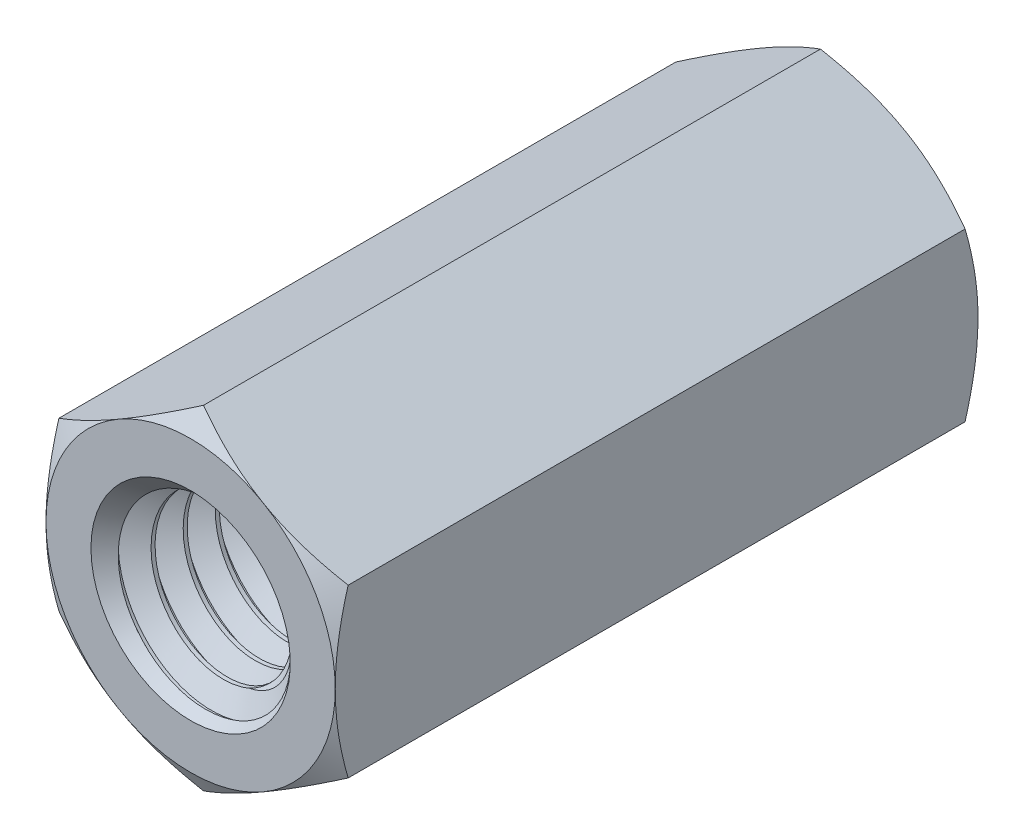
SolidWorks part; units mm, degrees
material "Brass"
ref_plane "Front Plane" through (0, 0, 0) normal (0, 0, 1) x (1, 0, 0)
ref_plane "Top Plane" through (0, 0, 0) normal (0, 1, 0) x (1, 0, 0)
ref_plane "Right Plane" through (0, 0, 0) normal (1, 0, 0) x (0, 0, -1)
sketch "Sketch3" plane through (0, 0, 0) normal (1, 0, 0) x (0, 0, -1)
  line L0 (-5, 0) -> (5, 0) construction
  line L1 (0, 2.25) -> (0, -2.25) construction
  line L2 (-5, 1.5) -> (-5, -1.5) construction
  point P2 (0.2, 0)
  point P3 (-0.2, 0)
  dimension "Length" = 10
  dimension "Min Thread Length" = 4.8
  dimension "D1" = 4.8
  dimension "Thread Dia" = 3
  dimension "Hex" = 4.5
sketch "Sketch1" plane through (0, 0, 0) normal (0, 0, 1) x (1, 0, 0)
  line L1 (0, 2.5981) -> (-2.25, 1.299)
  line L2 (-2.25, 1.299) -> (-2.25, -1.299)
  line L3 (-2.25, -1.299) -> (0, -2.5981)
  line L4 (0, -2.5981) -> (2.25, -1.299)
  line L5 (2.25, -1.299) -> (2.25, 1.299)
  line L6 (2.25, 1.299) -> (0, 2.5981)
  circle A0 centre (0, 0) radius 2.25 construction
  circle A1 centre (0, 0) radius 1.5
extrude "Extrude1" add sketch "Sketch1" along normal up to vertex (5 mm away) and the other way up to vertex (5 mm away) up to point (0, 0, 5) other way up to point (0, 0, -5)
sketch "Sketch11" plane through (0, 0, -5) normal (0, 0, -1) x (-1, 0, 0)
  circle A0 centre (0, 0) radius 1.5 construction
  circle A1 centre (0, 0) radius 1.5
curve "Helix/Spiral1" pitch 0.5 height 10.5 radius 1.5 centre (0, 0, -5) axis (0, 0, 1) start towards (0, 1, 0) parameters "Pitch"=0.5
sketch "Sketch12" plane through (0, 0, 0) normal (1, 0, 0) x (0, 0, -1)
  line L0 (5.4375, 1.5) -> (5, 1.5)
  line L1 (5.4375, 1.5) -> (5.25, 1.1752)
  line L2 (5.25, 1.1752) -> (5.1875, 1.1752)
  line L3 (5.1875, 1.1752) -> (5, 1.5)
  line L4 (5.2187, 1.1752) -> (5.2187, 1.5) construction
  line L5 (5.3437, 1.3376) -> (5.0937, 1.3376) construction
  dimension "D1" = 0.0625
  dimension "D2" = 0.25
  dimension "D3" = 60
sweep "Sweep1" add profiles "Sketch12" path "Helix/Spiral1"
sketch "Sketch6" plane through (0, 0, -5) normal (0, 0, -1) x (-1, 0, 0)
  line L6 (0, 2.5981) -> (-2.25, 1.299)
  line L7 (-2.25, 1.299) -> (-2.25, -1.299)
  line L8 (-2.25, -1.299) -> (0, -2.5981)
  line L9 (0, -2.5981) -> (2.25, -1.299)
  line L10 (2.25, -1.299) -> (2.25, 1.299)
  line L11 (2.25, 1.299) -> (0, 2.5981)
  line L12 (0, 2.5981) -> (-2.25, 1.299)
  line L13 (-2.25, 1.299) -> (-2.25, -1.299)
  line L14 (-2.25, -1.299) -> (0, -2.5981)
  line L15 (0, -2.5981) -> (2.25, -1.299)
  line L16 (2.25, -1.299) -> (2.25, 1.299)
  line L17 (2.25, 1.299) -> (0, 2.5981)
  dimension "D1" = 0
extrude "Extrude2" cut sketch "Sketch6" along normal through all
sketch "Sketch7" plane through (0, 0, -5) normal (0, 0, -1) x (-1, 0, 0)
  circle A2 centre (0, 0) radius 1.5508
  circle A3 centre (0, 0) radius 1.5508
  dimension "D1" = 0.0508
extrude "Extrude3" cut sketch "Sketch7" against normal through all draft 43
sketch "Sketch8" plane through (0, 0, -5) normal (0, 0, -1) x (-1, 0, 0)
  circle A0 centre (0, 0) radius 2.25 construction
  circle A1 centre (0, 0) radius 2.25
extrude "Extrude4" cut sketch "Sketch8" against normal through all draft 60 flip side to cut
mirror "Mirror1" about plane through (0, 0, 0) normal (0, 0, 1) of "Extrude2", "Extrude3", "Extrude4"
sketch "Sketch9" [suppressed] plane through (0, 0, 0) normal (1, 0, 0) x (0, 0, -1)
  line L1 (-1.2, 1.1353) -> (1.2, 1.1353)
  line L2 (-1.2, 1.1353) -> (-1.2, 0)
  line L3 (-1.2, 0) -> (1.2, 0)
  line L4 (1.2, 1.1353) -> (1.2, 0)
  line L7 (-6, 0) -> (6, 0) construction
revolve "Revolve" [suppressed] add sketch "Sketch9" angle 360 about L0
sketch "Sketch10" [suppressed] plane through (0, 0, 0) normal (1, 0, 0) x (0, 0, -1)
  line L0 (6, 1.25) -> (1.2, 1.25)
  line L1 (-6, 1.25) -> (-1.2, 1.25)
  line L2 (1.2, 1.25) -> (1.2, -1.25)
  line L3 (-6, -1.25) -> (-1.2, -1.25)
  line L4 (-1.2, 1.25) -> (-1.2, -1.25)
  line L5 (1.2, -1.25) -> (6, -1.25)
equation "\"D1@Sketch3\" = \"Min Thread Length@Sketch3\""
equation "\"D3@Helix/Spiral1\" = \"Length@Sketch3\"+\"Pitch@Helix/Spiral1\""
equation "\"D1@Sketch12\" = \"Pitch@Helix/Spiral1\"*.125"
equation "\"D2@Sketch12\" = \"Pitch@Helix/Spiral1\"*.5"
